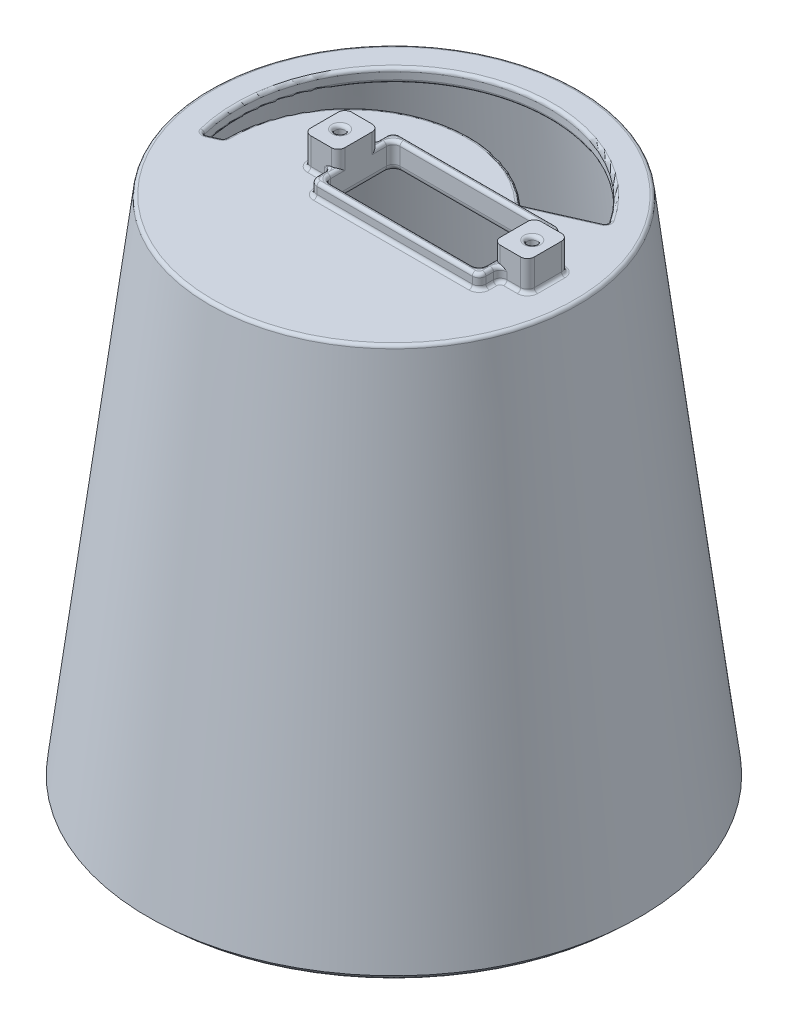
SolidWorks part; units mm, degrees
ref_plane "Front Plane" through (0, 0, 0) normal (0, 0, 1) x (1, 0, 0)
ref_plane "Top Plane" through (0, 0, 0) normal (0, 1, 0) x (1, 0, 0)
ref_plane "Right Plane" through (0, 0, 0) normal (1, 0, 0) x (0, 0, -1)
sketch "Sketch1" plane through (0, 0, 0) normal (0, 0, 1) x (1, 0, 0)
  line L0 (0, 0) -> (0, 95.25)
  line L1 (0, 95.25) -> (-34.3423, 95.25)
  line L2 (-34.3423, 95.25) -> (-46.0375, 0)
  line L3 (-46.0375, 0) -> (0, 0)
  circle A0 centre (-46.0375, 0) radius 1.5875
  dimension "D4" = 3.175
  dimension "D1" = 83
  dimension "D2" = 46.0375
  dimension "D3" = 95.25
  dimension "D5" = 46.0375
revolve "Revolve2" add sketch "Sketch1" angle 360 about L0 region at (-20.2248, 45.3365, 0)
shell "Shell1" thickness 2.54 removed face at (0, 0, -44.45)
sketch "Sketch2" plane through (0, 95.25, 0) normal (0, 1, 0) x (1, 0, 0)
  line L0 (-34.3423, 0) -> (34.3423, 0) construction
  line L2 (22.352, -6.477) -> (-6.604, -6.477)
  line L3 (22.352, -6.477) -> (22.352, 6.477)
  line L4 (22.352, 6.477) -> (-6.604, 6.477)
  line L5 (-6.604, -6.477) -> (-6.604, 6.477)
  line L6 (22.352, -6.477) -> (-6.604, 6.477) construction
  line L7 (22.352, 6.477) -> (-6.604, -6.477) construction
  circle A0 centre (0, 0) radius 34.3423 construction
  point P5 (7.874, 0)
  dimension "D1" = 6.604
  dimension "D2" = 12.954
  dimension "D3" = 28.956
extrude "Cut-Extrude1" cut sketch "Sketch2" against normal through all
sketch "Sketch3" plane through (0, 95.25, 0) normal (0, 1, 0) x (1, 0, 0)
  line L0 (-34.3423, 0) -> (34.3423, 0) construction
  line L1 (-6.604, 6.477) -> (-6.604, -6.477) construction
  line L2 (-12.954, 3.81) -> (-6.604, 3.81)
  line L3 (-12.954, 3.81) -> (-12.954, -3.81)
  line L4 (-12.954, -3.81) -> (-6.604, -3.81)
  line L5 (-6.604, 3.81) -> (-6.604, -3.81)
  line L6 (-12.954, 3.81) -> (-6.604, -3.81) construction
  line L7 (-12.954, -3.81) -> (-6.604, 3.81) construction
  circle A0 centre (0, 0) radius 34.3423 construction
  point P5 (-9.779, 0)
  dimension "D1" = 6.35
  dimension "D2" = 7.62
extrude "Boss-Extrude1" add sketch "Sketch3" along normal blind 5.588
ref_plane "Plane1" through (7.874, 0, 0) normal (1, 0, 0) x (0, 0, -1)
mirror "Mirror1" about plane through (7.874, 0, 0) normal (1, 0, 0) of "Boss-Extrude1"
sketch "Sketch4" plane through (0, 100.838, 0) normal (0, 1, 0) x (1, 0, 0)
  line L0 (-12.954, 0) -> (28.702, 0) construction
  line L1 (-12.954, 3.81) -> (-12.954, -3.81) construction
  line L2 (28.702, 3.81) -> (28.702, -3.81) construction
  line L3 (7.874, -3.7719) -> (7.874, 3.7719) construction
  circle A0 centre (-10.033, 0) radius 0.889
  dimension "D2" = 1.778
  dimension "D1" = 17.907
extrude "Cut-Extrude2" cut sketch "Sketch4" against normal through all
mirror "Mirror2" about plane through (7.874, 0, 0) normal (1, 0, 0) of "Cut-Extrude2"
sketch "Sketch5" plane through (0, 95.25, 0) normal (0, 1, 0) x (1, 0, 0)
  line L0 (-34.3423, 0) -> (34.3423, 0) construction
  line L1 (-6.604, 6.477) -> (-6.604, -6.477)
  line L2 (-6.604, -3.81) -> (-6.604, -6.477) construction
  line L3 (-6.604, -6.477) -> (22.352, -6.477)
  line L4 (22.352, -6.477) -> (22.352, 6.477)
  line L5 (22.352, 6.477) -> (-6.604, 6.477)
  line L6 (-7.874, 7.747) -> (23.622, 7.747)
  line L7 (23.622, 7.747) -> (23.622, -7.747)
  line L8 (23.622, -7.747) -> (-7.874, -7.747)
  line L9 (-7.874, -7.747) -> (-7.874, 7.747)
  circle A0 centre (0, 0) radius 34.3423 construction
  dimension "D1" = 1.27
  dimension "D2" = 1.27
  dimension "D3" = 1.27
  dimension "D4" = 1.27
extrude "Boss-Extrude2" add sketch "Sketch5" along normal blind 2.54
fillet "Fillet3" radius 1.27 15 edges at (-12.954, 98.044, -3.81) (-12.954, 98.044, 3.81) (28.702, 98.044, -3.81) (28.702, 98.044, 3.81) (23.622, 96.52, 3.81) (23.622, 96.52, -3.81) (23.622, 96.52, -7.747) (-7.874, 96.52, -7.747) (-7.874, 96.52, -3.81) (-7.874, 96.52, 3.81) (-7.874, 96.52, 7.747) (-6.604, 95.25, 6.477) (22.352, 95.25, 6.477) (22.352, 95.25, -6.477) (-6.604, 95.25, -6.477)
fillet "Fillet4" radius 1.27 4 edges at (22.352, 99.314, -3.81) (22.352, 99.314, 3.81)
fillet "Fillet5" radius 1.27 1 edges at (23.622, 96.52, 7.747)
fillet "Fillet6" radius 0.635 12 edges at (23.994, 97.79, -4.182) (23.622, 97.79, -5.7785) (23.25, 97.79, -7.375) (-8.246, 97.79, -4.182) (-7.874, 97.79, -5.7785) (-7.502, 97.79, -7.375) (22.352, 97.79, -3.8735) (21.98, 97.79, -6.105) (-6.604, 97.79, -3.8735) (-6.232, 97.79, -6.105) (7.874, 97.79, -7.747) (7.874, 97.79, -6.477)
fillet "Fillet7" radius 0.635 12 edges at (-8.246, 97.79, 4.182) (-7.874, 97.79, 5.7785) (-7.502, 97.79, 7.375) (23.994, 97.79, 4.182) (23.622, 97.79, 5.7785) (23.25, 97.79, 7.375) (-6.604, 97.79, 3.8735) (-6.232, 97.79, 6.105) (22.352, 97.79, 3.8735) (21.98, 97.79, 6.105) (7.874, 97.79, 7.747) (7.874, 97.79, 6.477)
fillet "Fillet8" radius 1.27 8 edges at (-6.232, 92.71, -6.105) (-6.604, 92.71, 0) (-6.232, 92.71, 6.105) (7.874, 92.71, 6.477) (21.98, 92.71, 6.105) (22.352, 92.71, 0) (21.98, 92.71, -6.105) (7.874, 92.71, -6.477)
fillet "Fillet9" radius 0.635 4 edges at (25.781, 92.71, -0.889) (-10.033, 92.71, -0.889) (25.781, 100.838, 0.889) (-10.033, 100.838, 0.889)
fillet "Fillet10" radius 0.635 24 edges at (-7.502, 95.25, 7.375) (-7.874, 95.25, 5.7785) (-8.246, 95.25, 4.182) (-12.582, 95.25, 3.438) (-12.954, 95.25, 0) (-12.582, 95.25, -3.438) (-8.246, 95.25, -4.182) (-7.874, 95.25, -5.7785) (-7.502, 95.25, -7.375) (7.874, 95.25, -7.747) (23.25, 95.25, -7.375) (23.622, 95.25, -5.7785) (23.994, 95.25, -4.182) (26.162, 95.25, -3.81) (28.33, 95.25, -3.438) (28.33, 95.25, 3.438) (26.162, 95.25, 3.81) (23.994, 95.25, 4.182) (23.622, 95.25, 5.7785) (23.25, 95.25, 7.375) (7.874, 95.25, 7.747) (28.702, 95.25, 0)
fillet "Fillet11" radius 0.635 1 edges at (0, 92.71, -32.0951)
fillet "Fillet12" radius 0.635 2 edges at (0, 0, -41.91) (0, 0, -44.45)
sketch "Sketch6" plane through (0, 95.25, 0) normal (0, 1, 0) x (1, 0, 0)
  line L0 (31.5333, 0) -> (-31.5333, 0) construction
  line L1 (27.6451, 8.7383) -> (-27.6451, -8.7383) construction
  line L2 (11.076, 26.7943) -> (-11.076, -26.7943) construction
  line L3 (24.615, 15.3202) -> (-27.8853, -7.9386)
  circle A0 centre (0, 0) radius 28.9933 construction
  circle A1 centre (0, 0) radius 31.5333 construction
  circle A2 centre (0, 0) radius 31.5333 construction
  circle A3 centre (0, 0) radius 28.9933
  circle A4 centre (-2.4615, -5.9546) radius 22.55
  dimension "D1" = 2.54
  dimension "D2" = 50
extrude "Cut-Extrude3" cut sketch "Sketch6" against normal blind 2.54 contours A4 A3 region at (-4.3537, 95.25, -17.2259)
fillet "Fillet13" radius 0.635 12 edges at (13.2045, 93.98, -10.2651) (18.9098, 92.71, -12.7927) (24.615, 93.98, -15.3202) (18.9098, 95.25, -12.7927) (-27.8853, 93.98, 7.9386) (-25.0004, 93.98, 6.6605) (-26.4428, 95.25, 7.2996) (-26.4428, 92.71, 7.2996) (-11.5954, 95.25, -14.6627) (-11.5954, 92.71, -14.6627) (-11.7438, 92.71, -26.5083) (-11.7438, 95.25, -26.5083)
fillet "Fillet14" radius 0.635 1 edges at (0, 95.25, -34.3423)
